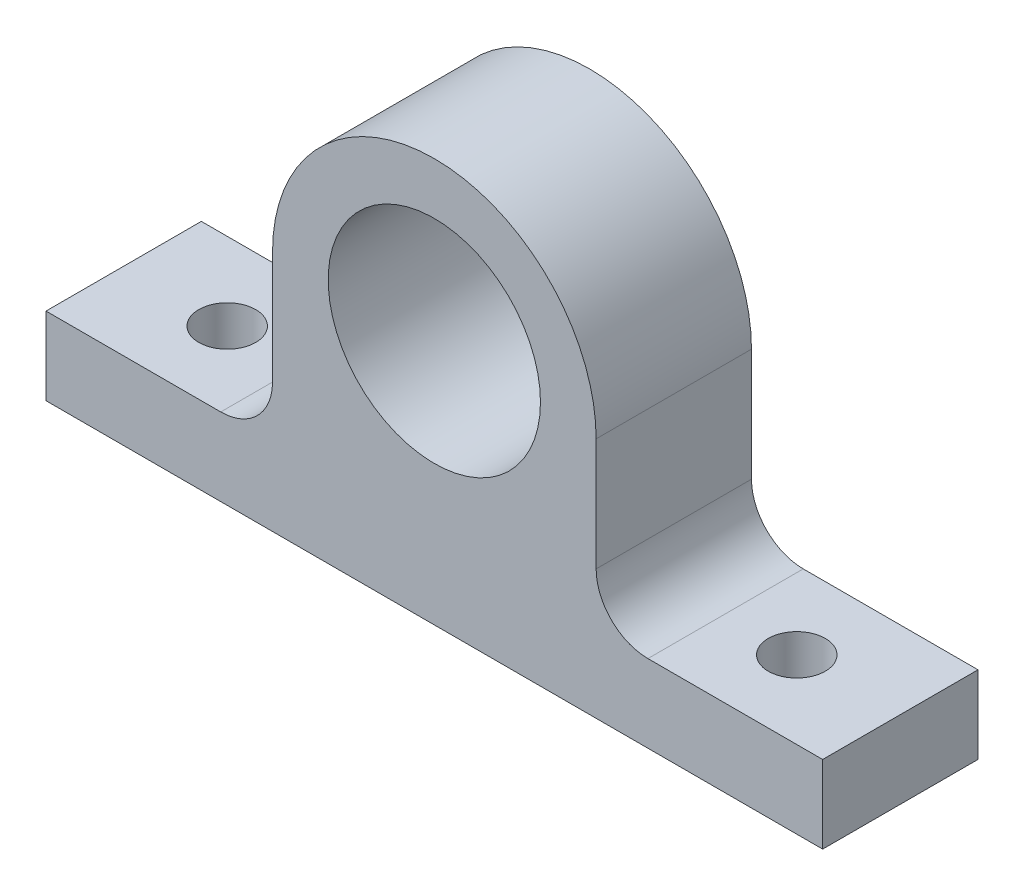
SolidWorks part; units mm, degrees
ref_plane "Front Plane" through (0, 0, 0) normal (0, 0, 1) x (1, 0, 0)
ref_plane "Top Plane" through (0, 0, 0) normal (0, 1, 0) x (1, 0, 0)
ref_plane "Right Plane" through (0, 0, 0) normal (1, 0, 0) x (0, 0, -1)
sketch "Sketch2" plane through (0, 0, 0) normal (0, 0, 1) x (1, 0, 0)
  line L0 (6.25, -6.5) -> (15, -6.5)
  line L1 (-6.25, 6.1) -> (6.25, 6.1)
  line L2 (-6.25, 6.1) -> (-6.25, -6.5)
  line L4 (6.25, 6.1) -> (6.25, -6.5)
  line L5 (-15, -9.5) -> (15, -9.5)
  line L6 (-15, -9.5) -> (-15, -6.5)
  line L7 (-15, -6.5) -> (-6.25, -6.5)
  line L8 (15, -9.5) -> (15, -6.5)
  circle A0 centre (0, 0) radius 4.1
  point P4 (0, 6.1)
  point P5 (0, -9.5)
  dimension "D1" = 6.1
  dimension "8.2" = 8.2
  dimension "D2" = 30
  dimension "D3" = 3
  dimension "D4" = 12.5
  dimension "D5" = 9.5
extrude "Boss-Extrude1" add sketch "Sketch2" along normal mid plane 6
fillet "Fillet1" 2 edges at (6.25, 6.1, 0) (-6.25, 6.1, 0) type full round first side face at (6.25, -0.2, 0) second side face at (-6.25, -0.2, 0) middle face at (0, 6.1, 0)
fillet "Fillet2" radius 2 2 edges at (6.25, -6.5, 0) (-6.25, -6.5, 0)
sketch "Sketch3" plane through (0, -6.5, 0) normal (0, 1, 0) x (1, 0, 0)
  line L0 (-15, -3) -> (-15, 3) construction
  line L1 (15, -3) -> (15, 3) construction
  circle A0 centre (-11, 0) radius 1.1
  circle A1 centre (11, 0) radius 1.1
  point P4 (0, 0)
  dimension "D3" = 2.2
  dimension "D1" = 4
  dimension "D2" = 4
extrude "Cut-Extrude1" cut sketch "Sketch3" against normal up to surface (3 mm away) up to face at (0, -9.5, 0)
